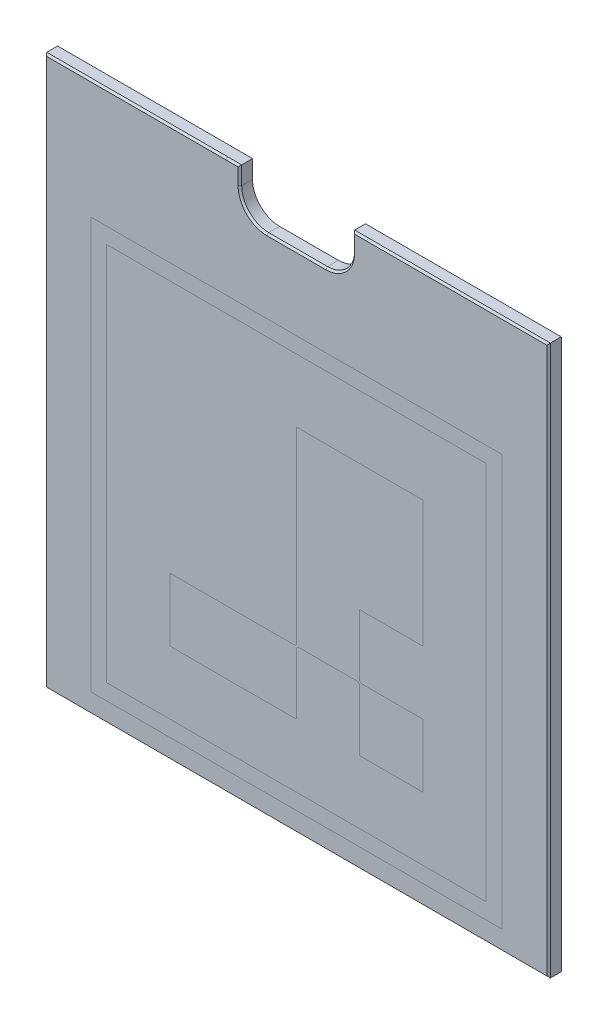
SolidWorks part; units mm, degrees
ref_plane "Front Plane" through (0, 0, 0) normal (0, 0, 1) x (1, 0, 0)
ref_plane "Top Plane" through (0, 0, 0) normal (0, 1, 0) x (1, 0, 0)
ref_plane "Right Plane" through (0, 0, 0) normal (1, 0, 0) x (0, 0, -1)
sketch "Sketch1" plane through (0, 0, 0) normal (0, 0, 1) x (1, 0, 0)
  line L0 (48, -68) -> (-48, -68) construction
  line L1 (56, -32.5) -> (56, -60) construction
  line L2 (56, 46) -> (56, -24.5) construction
  line L3 (-56, -24.5) -> (-56, 46) construction
  line L5 (-15, 54.4) -> (-15, 29) construction
  line L6 (-15, 29) -> (15, 29) construction
  line L7 (15, 29) -> (15, 54) construction
  line L8 (48, 54) -> (15, 54) construction
  line L9 (48, -68) -> (-48, -68) construction
  line L10 (56, -32.5) -> (56, -60) construction
  line L11 (56, 46) -> (56, -24.5) construction
  line L12 (-56, -24.5) -> (-56, 46) construction
  line L13 (-15, 54.4) -> (-48, 54.4) construction
  line L14 (-15, 54.4) -> (-15, 29) construction
  line L15 (-15, 29) -> (15, 29) construction
  line L16 (15, 29) -> (15, 54) construction
  line L17 (48, 54) -> (15, 54) construction
  line L18 (-15.25, 54.05) -> (-15.25, 28.75)
  line L19 (-55.65, 54.05) -> (-15.25, 54.05)
  line L20 (-55.65, 54.05) -> (-55.65, -67.65)
  line L21 (-55.65, -67.65) -> (55.825, -67.65)
  line L22 (55.825, 54.05) -> (55.825, -67.65)
  line L23 (-15.25, 28.75) -> (15.125, 28.75)
  line L24 (15.125, 28.75) -> (15.125, 54.05)
  line L25 (15.125, 54.05) -> (55.825, 54.05)
  circle A0 centre (-52, -64) radius 2.1 construction
  circle A3 centre (52, 50) radius 2.1 construction
  circle A4 centre (-52, 50) radius 2.1 construction
  circle A5 centre (-52, -64) radius 2.1 construction
  circle A6 centre (-52, 2.9) radius 2.15 construction
  circle A7 centre (52, 2.9) radius 2.15 construction
  circle A8 centre (52, 50) radius 2.1 construction
  circle A9 centre (-52, 50) radius 2.1 construction
  circle A10 centre (-52, 50) radius 1.35
  circle A11 centre (-52, 2.9) radius 1.35
  circle A12 centre (-52, -64) radius 1.35
  circle A13 centre (52, 50) radius 1.35
  circle A14 centre (52, 2.9) radius 1.35
  circle A15 centre (52, -64) radius 1.35
  circle A16 centre (-52, 2.9) radius 2.15 construction
  circle A17 centre (52, 2.9) radius 2.15 construction
  dimension "D5" = 2.7
  dimension "D1" = 0.35
  dimension "D2" = 0.35
  dimension "D3" = 0.35
  dimension "D4" = 0.35
  dimension "D6" = 0.25
  dimension "D7" = 0.25
  dimension "D8" = 0.25
extrude "Boss-Extrude1" add sketch "Sketch1" along normal blind 2.8
sketch "Sketch2" plane through (0, 0, 2.8) normal (0, 0, 1) x (1, 0, 0)
  line L5 (15.125, 28.75) -> (-15.25, 28.75) construction
  line L8 (-45.5, -63.25) -> (45.5, -63.25)
  line L9 (-45.5, -63.25) -> (-45.5, 27.75)
  line L10 (-45.5, 27.75) -> (45.5, 27.75)
  line L11 (45.5, -63.25) -> (45.5, 27.75)
  line L31 (-42, 24.25) -> (-28, 24.25)
  line L32 (-42, 24.25) -> (-42, 10.25)
  line L33 (-42, 10.25) -> (-28, 10.25)
  line L34 (-28, 24.25) -> (-28, 10.25)
  line L35 (-28, 24.25) -> (-14, 24.25)
  line L36 (-28, 24.25) -> (-28, 10.25)
  line L37 (-28, 10.25) -> (-14, 10.25)
  line L38 (-14, 24.25) -> (-14, 10.25)
  line L39 (-14, 24.25) -> (0, 24.25)
  line L40 (-14, 24.25) -> (-14, 10.25)
  line L41 (-14, 10.25) -> (0, 10.25)
  line L42 (0, 24.25) -> (0, 10.25)
  line L43 (0, 24.25) -> (14, 24.25)
  line L44 (0, 24.25) -> (0, 10.25)
  line L45 (0, 10.25) -> (14, 10.25)
  line L46 (14, 24.25) -> (14, 10.25)
  line L47 (14, 24.25) -> (28, 24.25)
  line L48 (14, 24.25) -> (14, 10.25)
  line L49 (14, 10.25) -> (28, 10.25)
  line L50 (28, 24.25) -> (28, 10.25)
  line L51 (28, 24.25) -> (42, 24.25)
  line L52 (28, 24.25) -> (28, 10.25)
  line L53 (28, 10.25) -> (42, 10.25)
  line L54 (42, 24.25) -> (42, 10.25)
  line L55 (-42, 10.25) -> (-28, 10.25)
  line L56 (-42, 10.25) -> (-42, -3.75)
  line L57 (-42, -3.75) -> (-28, -3.75)
  line L58 (-28, 10.25) -> (-28, -3.75)
  line L59 (-28, -3.75) -> (-14, -3.75)
  line L60 (-28, -3.75) -> (-28, 10.25)
  line L61 (-28, 10.25) -> (-14, 10.25)
  line L62 (-14, -3.75) -> (-14, 10.25)
  line L63 (-14, -3.75) -> (0, -3.75)
  line L64 (-14, -3.75) -> (-14, 10.25)
  line L65 (-14, 10.25) -> (0, 10.25)
  line L66 (0, -3.75) -> (0, 10.25)
  line L67 (0, -3.75) -> (14, -3.75)
  line L68 (0, -3.75) -> (0, 10.25)
  line L69 (0, 10.25) -> (14, 10.25)
  line L70 (14, -3.75) -> (14, 10.25)
  line L71 (14, -3.75) -> (28, -3.75)
  line L72 (14, -3.75) -> (14, 10.25)
  line L73 (14, 10.25) -> (28, 10.25)
  line L74 (28, -3.75) -> (28, 10.25)
  line L75 (28, -3.75) -> (42, -3.75)
  line L76 (28, -3.75) -> (28, 10.25)
  line L77 (28, 10.25) -> (42, 10.25)
  line L78 (42, -3.75) -> (42, 10.25)
  line L79 (42, -3.75) -> (28, -3.75)
  line L80 (42, -3.75) -> (42, -17.75)
  line L81 (42, -17.75) -> (28, -17.75)
  line L82 (28, -3.75) -> (28, -17.75)
  line L83 (14, -3.75) -> (28, -3.75)
  line L84 (14, -3.75) -> (14, -17.75)
  line L85 (14, -17.75) -> (28, -17.75)
  line L86 (28, -3.75) -> (28, -17.75)
  line L87 (0, -3.75) -> (14, -3.75)
  line L88 (0, -3.75) -> (0, -17.75)
  line L89 (0, -17.75) -> (14, -17.75)
  line L90 (14, -3.75) -> (14, -17.75)
  line L91 (-14, -3.75) -> (0, -3.75)
  line L92 (-14, -3.75) -> (-14, -17.75)
  line L93 (-14, -17.75) -> (0, -17.75)
  line L94 (0, -3.75) -> (0, -17.75)
  line L95 (-28, -3.75) -> (-14, -3.75)
  line L96 (-28, -3.75) -> (-28, -17.75)
  line L97 (-28, -17.75) -> (-14, -17.75)
  line L98 (-14, -3.75) -> (-14, -17.75)
  line L99 (-42, -3.75) -> (-28, -3.75)
  line L100 (-42, -3.75) -> (-42, -17.75)
  line L101 (-42, -17.75) -> (-28, -17.75)
  line L102 (-28, -3.75) -> (-28, -17.75)
  line L103 (-42, -17.75) -> (-28, -17.75)
  line L104 (-42, -17.75) -> (-42, -31.75)
  line L105 (-42, -31.75) -> (-28, -31.75)
  line L106 (-28, -17.75) -> (-28, -31.75)
  line L107 (-28, -31.75) -> (-14, -31.75)
  line L108 (-28, -31.75) -> (-28, -17.75)
  line L109 (-28, -17.75) -> (-14, -17.75)
  line L110 (-14, -31.75) -> (-14, -17.75)
  line L111 (-14, -17.75) -> (0, -17.75)
  line L112 (-14, -17.75) -> (-14, -31.75)
  line L113 (-14, -31.75) -> (0, -31.75)
  line L114 (0, -17.75) -> (0, -31.75)
  line L115 (0, -31.75) -> (14, -31.75)
  line L116 (0, -31.75) -> (0, -17.75)
  line L117 (0, -17.75) -> (14, -17.75)
  line L118 (14, -31.75) -> (14, -17.75)
  line L119 (14, -31.75) -> (28, -31.75)
  line L120 (14, -31.75) -> (14, -17.75)
  line L121 (14, -17.75) -> (28, -17.75)
  line L122 (28, -31.75) -> (28, -17.75)
  line L123 (28, -31.75) -> (42, -31.75)
  line L124 (28, -31.75) -> (28, -17.75)
  line L125 (28, -17.75) -> (42, -17.75)
  line L126 (42, -31.75) -> (42, -17.75)
  line L127 (-42, -31.75) -> (-28, -31.75)
  line L128 (-42, -31.75) -> (-42, -45.75)
  line L129 (-42, -45.75) -> (-28, -45.75)
  line L130 (-28, -31.75) -> (-28, -45.75)
  line L131 (-28, -45.75) -> (-14, -45.75)
  line L132 (-28, -45.75) -> (-28, -31.75)
  line L133 (-28, -31.75) -> (-14, -31.75)
  line L134 (-14, -45.75) -> (-14, -31.75)
  line L135 (-14, -45.75) -> (0, -45.75)
  line L136 (-14, -45.75) -> (-14, -31.75)
  line L137 (-14, -31.75) -> (0, -31.75)
  line L138 (0, -45.75) -> (0, -31.75)
  line L139 (0, -45.75) -> (14, -45.75)
  line L140 (0, -45.75) -> (0, -31.75)
  line L141 (0, -31.75) -> (14, -31.75)
  line L142 (14, -45.75) -> (14, -31.75)
  line L143 (14, -45.75) -> (28, -45.75)
  line L144 (14, -45.75) -> (14, -31.75)
  line L145 (14, -31.75) -> (28, -31.75)
  line L146 (28, -45.75) -> (28, -31.75)
  line L147 (28, -45.75) -> (42, -45.75)
  line L148 (28, -45.75) -> (28, -31.75)
  line L149 (28, -31.75) -> (42, -31.75)
  line L150 (42, -45.75) -> (42, -31.75)
  line L151 (42, -45.75) -> (28, -45.75)
  line L152 (42, -45.75) -> (42, -59.75)
  line L153 (42, -59.75) -> (28, -59.75)
  line L154 (28, -45.75) -> (28, -59.75)
  line L155 (28, -59.75) -> (14, -59.75)
  line L156 (28, -59.75) -> (28, -45.75)
  line L157 (28, -45.75) -> (14, -45.75)
  line L158 (14, -59.75) -> (14, -45.75)
  line L159 (0, -45.75) -> (14, -45.75)
  line L160 (0, -45.75) -> (0, -59.75)
  line L161 (0, -59.75) -> (14, -59.75)
  line L162 (14, -45.75) -> (14, -59.75)
  line L163 (-14, -45.75) -> (0, -45.75)
  line L164 (-14, -45.75) -> (-14, -59.75)
  line L165 (-14, -59.75) -> (0, -59.75)
  line L166 (0, -45.75) -> (0, -59.75)
  line L167 (-28, -45.75) -> (-14, -45.75)
  line L168 (-28, -45.75) -> (-28, -59.75)
  line L169 (-28, -59.75) -> (-14, -59.75)
  line L170 (-14, -45.75) -> (-14, -59.75)
  line L171 (-42, -45.75) -> (-28, -45.75)
  line L172 (-42, -45.75) -> (-42, -59.75)
  line L173 (-42, -59.75) -> (-28, -59.75)
  line L174 (-28, -45.75) -> (-28, -59.75)
  point P3 (0, 27.75)
  point P58 (-45.5, -17.75)
  dimension "D1" = 1
  dimension "D2" = 91
  dimension "D3" = 14
sketch "Sketch3" plane through (0, 0, 2.8) normal (0, 0, 1) x (1, 0, 0)
  circle A0 centre (-52, 50) radius 2.5
  circle A1 centre (-52, 2.9) radius 2.5
  circle A2 centre (-52, -64) radius 2.5
  circle A3 centre (52, -64) radius 2.5
  circle A4 centre (52, 2.9) radius 2.5
  circle A5 centre (52, 50) radius 2.5
  dimension "D1" = 5
extrude "Cut-Extrude1" cut sketch "Sketch3" against normal blind 2.2
sketch "Sketch4" plane through (0, 0, 0) normal (0, 0, -1) x (-1, 0, 0)
  line L0 (-15.125, 28.75) -> (15.25, 28.75) construction
  line L1 (-45.65, -57.65) -> (45.65, -57.65)
  line L2 (-45.65, -57.65) -> (-45.65, 27.75)
  line L3 (-45.65, 27.75) -> (45.65, 27.75)
  line L4 (45.65, -57.65) -> (45.65, 27.75)
  line L5 (-45.65, -57.65) -> (45.65, 27.75) construction
  line L6 (-45.65, 27.75) -> (45.65, -57.65) construction
  line L7 (55.65, 54.05) -> (55.65, -67.65) construction
  line L8 (55.65, -67.65) -> (-55.825, -67.65) construction
  point P0 (0, -14.95)
  point P9 (0, 27.75)
  dimension "D1" = 1
  dimension "D2" = 10
  dimension "D3" = 10
extrude "Cut-Extrude2" cut sketch "Sketch4" against normal blind 1.5
sketch "Sketch5" plane through (0, 0, 0.6) normal (0, 0, 1) x (1, 0, 0)
  line L2 (-53.35, 47.8958) -> (-53.35, 52.1042)
  line L4 (-50.65, 47.8958) -> (-50.65, 52.1042)
  line L5 (-53.35, 47.8958) -> (-50.65, 52.1042) construction
  line L6 (-53.35, 52.1042) -> (-50.65, 47.8958) construction
  line L8 (-53.35, 0.7958) -> (-53.35, 5.0042)
  line L10 (-50.65, 0.7958) -> (-50.65, 5.0042)
  line L11 (-53.35, 0.7958) -> (-50.65, 5.0042) construction
  line L12 (-53.35, 5.0042) -> (-50.65, 0.7958) construction
  line L14 (-53.35, -66.1042) -> (-53.35, -61.8958)
  line L16 (-50.65, -66.1042) -> (-50.65, -61.8958)
  line L17 (-53.35, -66.1042) -> (-50.65, -61.8958) construction
  line L18 (-53.35, -61.8958) -> (-50.65, -66.1042) construction
  circle A0 centre (-52, 50) radius 2.5 construction
  circle A1 centre (-52, 50) radius 1.35 construction
  arc A2 (-50.65, 52.1042) -> (-53.35, 52.1042) centre (-52, 50) ccw
  arc A3 (-53.35, 47.8958) -> (-50.65, 47.8958) centre (-52, 50) ccw
  circle A4 centre (-52, 2.9) radius 2.5 construction
  circle A5 centre (-52, 2.9) radius 1.35 construction
  circle A6 centre (-52, 2.9) radius 2.5 construction
  arc A7 (-50.65, 5.0042) -> (-53.35, 5.0042) centre (-52, 2.9) ccw
  arc A8 (-53.35, 0.7958) -> (-50.65, 0.7958) centre (-52, 2.9) ccw
  circle A9 centre (-52, -64) radius 2.5 construction
  circle A10 centre (-52, -64) radius 1.35 construction
  circle A11 centre (-52, -64) radius 2.5 construction
  arc A12 (-50.65, -61.8958) -> (-53.35, -61.8958) centre (-52, -64) ccw
  arc A13 (-53.35, -66.1042) -> (-50.65, -66.1042) centre (-52, -64) ccw
  point P0 (-52, 50)
  point P10 (-52, 2.9)
  point P22 (-52, -64)
extrude "Cut-Extrude3" cut sketch "Sketch5" against normal blind 0.2
sketch "Sketch6" plane through (0, 0, 0.4) normal (0, 0, 1) x (1, 0, 0)
  line L0 (-50.65, -66.1042) -> (-50.65, -61.8958) construction
  line L1 (-53.35, -65.35) -> (-50.65, -65.35)
  line L2 (-53.35, -65.35) -> (-53.35, -62.65)
  line L3 (-53.35, -62.65) -> (-50.65, -62.65)
  line L4 (-50.65, -65.35) -> (-50.65, -62.65)
  line L5 (-53.35, -65.35) -> (-50.65, -62.65) construction
  line L6 (-53.35, -62.65) -> (-50.65, -65.35) construction
  line L7 (-50.65, 0.7958) -> (-50.65, 5.0042) construction
  line L8 (-53.35, 1.55) -> (-50.65, 1.55)
  line L9 (-53.35, 1.55) -> (-53.35, 4.25)
  line L10 (-53.35, 4.25) -> (-50.65, 4.25)
  line L11 (-50.65, 1.55) -> (-50.65, 4.25)
  line L12 (-53.35, 1.55) -> (-50.65, 4.25) construction
  line L13 (-53.35, 4.25) -> (-50.65, 1.55) construction
  line L14 (-50.65, 47.8958) -> (-50.65, 52.1042) construction
  line L15 (-53.35, 48.65) -> (-50.65, 48.65)
  line L16 (-53.35, 48.65) -> (-53.35, 51.35)
  line L17 (-53.35, 51.35) -> (-50.65, 51.35)
  line L18 (-50.65, 48.65) -> (-50.65, 51.35)
  line L19 (-53.35, 48.65) -> (-50.65, 51.35) construction
  line L20 (-53.35, 51.35) -> (-50.65, 48.65) construction
  arc A0 (-50.65, -64) -> (-53.35, -64) centre (-52, -64) ccw construction
  arc A1 (-50.65, 2.9) -> (-53.35, 2.9) centre (-52, 2.9) ccw construction
  arc A2 (-50.65, 50) -> (-53.35, 50) centre (-52, 50) ccw construction
  point P0 (-52, -64)
  point P11 (-52, 2.9)
  point P22 (-52, 50)
extrude "Cut-Extrude4" cut sketch "Sketch6" against normal blind 0.2
mirror "Mirror1" about plane through (0, 0, 0) normal (1, 0, 0) of "Cut-Extrude4", "Cut-Extrude3"
chamfer "Chamfer1" distance 0.4 angle 45 8 edges at (0.0875, -67.65, 2.8) (55.825, -6.8, 2.8) (35.475, 54.05, 2.8) (15.125, 41.4, 2.8) (-0.0625, 28.75, 2.8) (-15.25, 41.4, 2.8) (-35.45, 54.05, 2.8) (-55.65, -6.8, 2.8)
sketch "Sketch7" plane through (0, 0, 2.8) normal (0, 0, 1) x (1, 0, 0)
  line L0 (28, 24.25) -> (42, 24.25) construction
  line L1 (14, 24.25) -> (28, 24.25) construction
  line L2 (0, 24.25) -> (14, 24.25) construction
  line L3 (-14, 24.25) -> (0, 24.25) construction
  line L4 (-28, 24.25) -> (-14, 24.25) construction
  line L5 (-42, 24.25) -> (-28, 24.25) construction
  line L6 (-42, 24.25) -> (-42, 10.25) construction
  line L7 (-42, 10.25) -> (-42, -3.75) construction
  line L8 (-42, -3.75) -> (-42, -17.75) construction
  line L9 (-42, -17.75) -> (-42, -31.75) construction
  line L10 (-42, -31.75) -> (-42, -45.75) construction
  line L11 (-42, -45.75) -> (-42, -59.75) construction
  line L12 (-42, -59.75) -> (-28, -59.75) construction
  line L13 (-28, -59.75) -> (-14, -59.75) construction
  line L14 (-14, -59.75) -> (0, -59.75) construction
  line L15 (0, -59.75) -> (14, -59.75) construction
  line L16 (28, -59.75) -> (14, -59.75) construction
  line L17 (42, -59.75) -> (28, -59.75) construction
  line L18 (42, -45.75) -> (42, -59.75) construction
  line L19 (42, -45.75) -> (42, -31.75) construction
  line L20 (42, -31.75) -> (42, -17.75) construction
  line L21 (42, -3.75) -> (42, -17.75) construction
  line L22 (42, -3.75) -> (42, 10.25) construction
  line L23 (42, 24.25) -> (42, 10.25) construction
  line L24 (45.5, -63.25) -> (45.5, 27.75) construction
  line L25 (-45.5, -63.25) -> (45.5, -63.25) construction
  line L26 (-45.5, -63.25) -> (-45.5, 27.75) construction
  line L27 (-45.5, 27.75) -> (45.5, 27.75) construction
  line L28 (28, 24.25) -> (42, 24.25)
  line L29 (14, 24.25) -> (28, 24.25)
  line L30 (0, 24.25) -> (14, 24.25)
  line L31 (-14, 24.25) -> (0, 24.25)
  line L32 (-28, 24.25) -> (-14, 24.25)
  line L33 (-42, 24.25) -> (-28, 24.25)
  line L34 (-42, 24.25) -> (-42, 10.25)
  line L35 (-42, 10.25) -> (-42, -3.75)
  line L36 (-42, -3.75) -> (-42, -17.75)
  line L37 (-42, -17.75) -> (-42, -31.75)
  line L38 (-42, -31.75) -> (-42, -45.75)
  line L39 (-42, -45.75) -> (-42, -59.75)
  line L40 (-42, -59.75) -> (-28, -59.75)
  line L41 (-28, -59.75) -> (-14, -59.75)
  line L42 (-14, -59.75) -> (0, -59.75)
  line L43 (0, -59.75) -> (14, -59.75)
  line L44 (28, -59.75) -> (14, -59.75)
  line L45 (42, -59.75) -> (28, -59.75)
  line L46 (42, -45.75) -> (42, -59.75)
  line L47 (42, -45.75) -> (42, -31.75)
  line L48 (42, -31.75) -> (42, -17.75)
  line L49 (42, -3.75) -> (42, -17.75)
  line L50 (42, -3.75) -> (42, 10.25)
  line L51 (42, 24.25) -> (42, 10.25)
  line L52 (45.5, -63.25) -> (45.5, 27.75)
  line L53 (-45.5, -63.25) -> (45.5, -63.25)
  line L54 (-45.5, -63.25) -> (-45.5, 27.75)
  line L55 (-45.5, 27.75) -> (45.5, 27.75)
extrude "Cut-Extrude5" cut sketch "Sketch7" against normal blind 0.4
sketch "Sketch8" plane through (0, 0, 2.4) normal (0, 0, 1) x (1, 0, 0)
  line L0 (-42, -59.75) -> (42, -59.75) construction
  line L1 (42, -59.75) -> (42, 24.25) construction
  line L2 (42, 24.25) -> (-42, 24.25) construction
  line L3 (-42, 24.25) -> (-42, -59.75) construction
  line L4 (-45.5, -63.25) -> (45.5, -63.25)
  line L5 (45.5, -63.25) -> (45.5, 27.75)
  line L6 (45.5, 27.75) -> (-45.5, 27.75)
  line L7 (-45.5, 27.75) -> (-45.5, -63.25)
  line L8 (-45.5, -63.25) -> (45.5, -63.25)
  line L9 (45.5, -63.25) -> (45.5, 27.75)
  line L10 (45.5, 27.75) -> (-45.5, 27.75)
  line L11 (-45.5, 27.75) -> (-45.5, -63.25)
  line L12 (-42, -59.75) -> (42, -59.75)
  line L13 (42, -59.75) -> (42, 24.25)
  line L14 (42, 24.25) -> (-42, 24.25)
  line L15 (-42, 24.25) -> (-42, -59.75)
  dimension "D1" = 0
extrude "Boss-Extrude2" add sketch "Sketch8" along normal up to surface (0.4 mm away) separate body up to face at (0, -17.75, 2.8)
sketch "Sketch9" plane through (0, 0, 2.8) normal (0, 0, 1) x (1, 0, 0)
  line L40 (-28, -31.75) -> (-28, -45.75) construction
  line L41 (-28, -31.75) -> (-14, -31.75) construction
  line L42 (-14, -31.75) -> (0, -31.75) construction
  line L43 (0, -17.75) -> (0, -31.75) construction
  line L44 (0, -3.75) -> (0, -17.75) construction
  line L45 (0, -3.75) -> (0, 10.25) construction
  line L46 (0, 10.25) -> (14, 10.25) construction
  line L47 (14, 10.25) -> (28, 10.25) construction
  line L48 (28, -3.75) -> (28, 10.25) construction
  line L49 (28, -3.75) -> (28, -17.75) construction
  line L50 (14, -17.75) -> (28, -17.75) construction
  line L51 (14, -31.75) -> (14, -17.75) construction
  line L52 (14, -31.75) -> (28, -31.75) construction
  line L53 (28, -45.75) -> (28, -31.75) construction
  line L54 (14, -45.75) -> (28, -45.75) construction
  line L55 (14, -45.75) -> (14, -31.75) construction
  line L56 (0, -31.75) -> (14, -31.75) construction
  line L57 (0, -45.75) -> (0, -31.75) construction
  line L58 (-14, -45.75) -> (0, -45.75) construction
  line L59 (-28, -45.75) -> (-14, -45.75) construction
  line L60 (-28, -31.75) -> (-28, -45.75)
  line L61 (-28, -31.75) -> (-14, -31.75)
  line L62 (-14, -31.75) -> (-0.3536, -31.75)
  line L63 (0, -17.75) -> (0, -31.3964)
  line L64 (0, -3.75) -> (0, -17.75)
  line L65 (0, -3.75) -> (0, 10.25)
  line L66 (0, 10.25) -> (14, 10.25)
  line L67 (14, 10.25) -> (28, 10.25)
  line L68 (28, -3.75) -> (28, 10.25)
  line L69 (28, -3.75) -> (28, -17.75)
  line L70 (14, -17.75) -> (28, -17.75)
  line L71 (14, -31.3964) -> (14, -17.75)
  line L72 (14.3536, -31.75) -> (28, -31.75)
  line L73 (28, -45.75) -> (28, -31.75)
  line L74 (14, -45.75) -> (28, -45.75)
  line L75 (14, -45.75) -> (14, -32.1036)
  line L76 (0.3536, -31.75) -> (13.6464, -31.75)
  line L77 (0, -45.75) -> (0, -32.1036)
  line L78 (-14, -45.75) -> (0, -45.75)
  line L79 (-28, -45.75) -> (-14, -45.75)
  line L80 (0, -31.3964) -> (-0.3536, -31.75)
  line L81 (0, -32.1036) -> (0.3536, -31.75)
  line L82 (13.6464, -31.75) -> (14, -32.1036)
  line L83 (14.3536, -31.75) -> (14, -31.3964)
  dimension "D1" = 45
  dimension "D2" = 0.5
  dimension "D3" = 45
  dimension "D4" = 0.5
extrude "Cut-Extrude6" cut sketch "Sketch9" against normal blind 0.4 contours L63 L76 L71 L70 L69 L68 L67 L66 L65 L64 region at (7, -19.502, 2.8)
sketch "Sketch10" plane through (0, 0, 2.4) normal (0, 0, 1) x (1, 0, 0)
  line L42 (28, -31.75) -> (14.3536, -31.75)
  line L43 (14.3536, -31.75) -> (14, -31.3964)
  line L44 (14, -31.3964) -> (14, -17.75)
  line L45 (14, -17.75) -> (28, -17.75)
  line L46 (28, -17.75) -> (28, 10.25)
  line L47 (28, 10.25) -> (0, 10.25)
  line L48 (0, 10.25) -> (0, -31.3964)
  line L49 (0, -31.3964) -> (-0.3536, -31.75)
  line L50 (-0.3536, -31.75) -> (-28, -31.75)
  line L51 (-28, -31.75) -> (-28, -45.75)
  line L52 (-28, -45.75) -> (0, -45.75)
  line L53 (0, -45.75) -> (0, -32.1036)
  line L54 (0, -32.1036) -> (0.3536, -31.75)
  line L55 (0.3536, -31.75) -> (13.6464, -31.75)
  line L56 (13.6464, -31.75) -> (14, -32.1036)
  line L57 (14, -32.1036) -> (14, -45.75)
  line L58 (14, -45.75) -> (28, -45.75)
  line L59 (28, -45.75) -> (28, -31.75)
  line L60 (28, -31.75) -> (14.3536, -31.75)
  line L61 (14.3536, -31.75) -> (14, -31.3964)
  line L62 (14, -31.3964) -> (14, -17.75)
  line L63 (14, -17.75) -> (28, -17.75)
  line L64 (28, -17.75) -> (28, 10.25)
  line L65 (28, 10.25) -> (0, 10.25)
  line L66 (0, 10.25) -> (0, -31.3964)
  line L67 (0, -31.3964) -> (-0.3536, -31.75)
  line L68 (-0.3536, -31.75) -> (-28, -31.75)
  line L69 (-28, -31.75) -> (-28, -45.75)
  line L70 (-28, -45.75) -> (0, -45.75)
  line L71 (0, -45.75) -> (0, -32.1036)
  line L72 (0, -32.1036) -> (0.3536, -31.75)
  line L73 (0.3536, -31.75) -> (13.6464, -31.75)
  line L74 (13.6464, -31.75) -> (14, -32.1036)
  line L75 (14, -32.1036) -> (14, -45.75)
  line L76 (14, -45.75) -> (28, -45.75)
  line L77 (28, -45.75) -> (28, -31.75)
  line M69 (28, -31.75) -> (14.3536, -31.75)
  line M70 (14.3536, -31.75) -> (14, -31.3964)
  line M71 (14, -31.3964) -> (14, -17.75)
  line M72 (14, -17.75) -> (28, -17.75)
  line M73 (28, -17.75) -> (28, 10.25)
  line M74 (28, 10.25) -> (0, 10.25)
  line M75 (0, 10.25) -> (0, -31.3964)
  line M76 (0, -31.3964) -> (-0.3536, -31.75)
  line M77 (-0.3536, -31.75) -> (-28, -31.75)
  line M78 (-28, -31.75) -> (-28, -45.75)
  line M79 (-28, -45.75) -> (0, -45.75)
  line M80 (0, -45.75) -> (0, -32.1036)
  line M81 (0, -32.1036) -> (0.3536, -31.75)
  line M82 (0.3536, -31.75) -> (13.6464, -31.75)
  line M83 (13.6464, -31.75) -> (14, -32.1036)
  line M84 (14, -32.1036) -> (14, -45.75)
  line M85 (14, -45.75) -> (28, -45.75)
  line M86 (28, -45.75) -> (28, -31.75)
  dimension "D1" = 0
extrude "Boss-Extrude3" add sketch "Sketch10" along normal up to surface (0.4 mm away) separate body contours M86 M69 M70 M71 M72 M73 M74 M75 M76 M77 M78 M79 M80 M81 M82 M83 M84 M85 region at (7, -19.502, 2.4) up to face at (0, -17.75, 2.8)
sketch "Sketch11" plane through (0, 0, 2.8) normal (0, 0, 1) x (1, 0, 0)
  line L0 (15.125, 54.05) -> (55.825, 54.05) construction
  line L1 (-15.65, 28.35) -> (15.525, 28.35)
  line L2 (-15.65, 28.35) -> (-15.65, 54.05)
  line L3 (-15.65, 54.05) -> (15.525, 54.05)
  line L4 (15.525, 28.35) -> (15.525, 54.05)
  line L5 (15.525, 53.65) -> (15.525, 28.35) construction
extrude "Boss-Extrude4" add sketch "Sketch11" against normal up to surface (2.8 mm away) up to face at (0, -14.95, 0)
chamfer "Chamfer2" distance 0.4 angle 45 1 edges at (-0.0625, 54.05, 2.8)
sketch "Sketch12" plane through (0, 0, 2.8) normal (0, 0, 1) x (1, 0, 0)
  circle A0 centre (52, -64) radius 2.5 construction
  circle A1 centre (52, 50) radius 2.5 construction
  circle A2 centre (52, 2.9) radius 2.5 construction
  circle A3 centre (-52, -64) radius 2.5 construction
  circle A4 centre (-52, 2.9) radius 2.5 construction
  circle A5 centre (-52, 50) radius 2.5 construction
  circle A6 centre (52, -64) radius 2.5
  circle A7 centre (52, 50) radius 2.5
  circle A8 centre (52, 2.9) radius 2.5
  circle A9 centre (-52, -64) radius 2.5
  circle A10 centre (-52, 2.9) radius 2.5
  circle A11 centre (-52, 50) radius 2.5
extrude "Boss-Extrude5" add sketch "Sketch12" against normal up to surface (2.8 mm away) up to face at (0.0875, -6.8, 0)
sketch "Sketch13" plane through (0, 0, 0) normal (0, 0, -1) x (-1, 0, 0)
  line L0 (-55.825, -67.65) -> (-55.825, 54.05) construction
  line L1 (-50.825, 49.05) -> (50.825, 49.05) construction
  line L2 (-50.825, 49.05) -> (-50.825, -62.65) construction
  line L3 (-50.825, -62.65) -> (50.825, -62.65) construction
  line L4 (50.825, 49.05) -> (50.825, -62.65) construction
  line L5 (-55.825, 54.05) -> (55.65, 54.05) construction
  line L6 (55.65, -67.65) -> (-55.825, -67.65) construction
  circle A0 centre (-50.825, 49.05) radius 3.2
  circle A1 centre (50.825, 49.05) radius 3.2
  circle A2 centre (50.825, -62.65) radius 3.2
  circle A3 centre (-50.825, -62.65) radius 3.2
  circle A4 centre (-50.825, -6.8) radius 3.2
  circle A5 centre (50.825, -6.8) radius 3.2
  point P4 (0, 49.05)
  dimension "D1" = 6.4
  dimension "D2" = 5
  dimension "D3" = 5
  dimension "D4" = 5
extrude "Cut-Extrude7" cut sketch "Sketch13" against normal blind 1.2
sketch "Sketch14" plane through (0, 0, 2.8) normal (0, 0, 1) x (1, 0, 0)
  line L0 (-55.65, 54.05) -> (-15.65, 54.05) construction
  line L1 (-12.5, 54.05) -> (12.5, 54.05)
  line L2 (-12.5, 54.05) -> (-12.5, 44.05)
  line L3 (-12.5, 44.05) -> (12.5, 44.05)
  line L4 (12.5, 54.05) -> (12.5, 44.05)
  point P6 (0, 44.05)
  dimension "D1" = 25
  dimension "D2" = 10
extrude "Cut-Extrude8" cut sketch "Sketch14" against normal through all
fillet "Fillet1" radius 6 2 edges at (12.5, 44.05, 1.4) (-12.5, 44.05, 1.4)
chamfer "Chamfer3" distance 0.4 angle 45 5 edges at (-12.5, 51.85, 2.8) (12.5, 51.85, 2.8) (-10.7426, 45.8074, 2.8) (10.7426, 45.8074, 2.8) (0, 44.05, 2.8)
